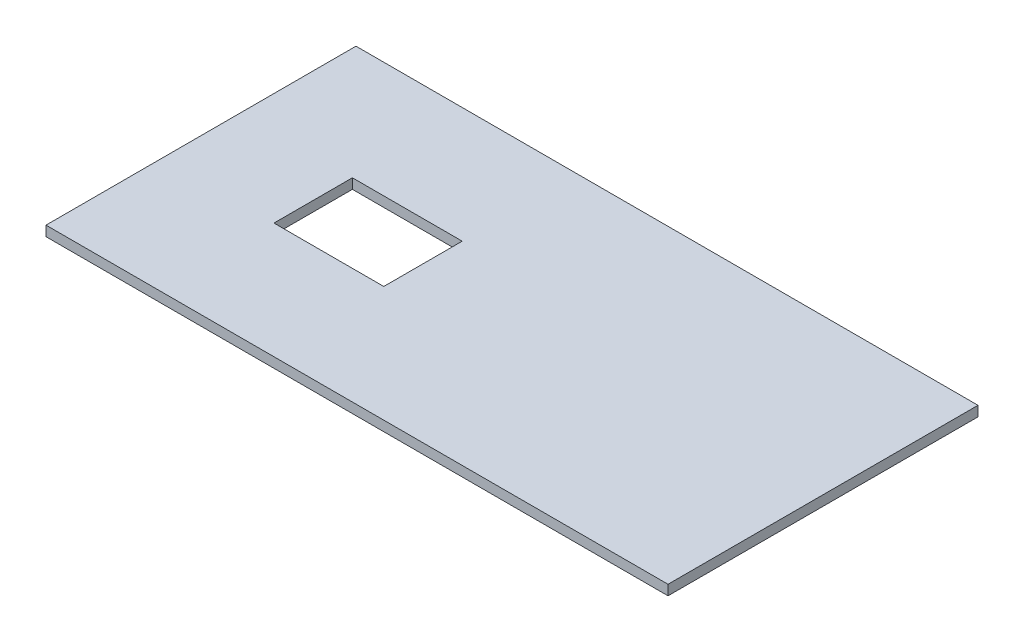
SolidWorks part; units mm, degrees
ref_plane "Front Plane" through (0, 0, 0) normal (0, 0, 1) x (1, 0, 0)
ref_plane "Top Plane" through (0, 0, 0) normal (0, 1, 0) x (1, 0, 0)
ref_plane "Right Plane" through (0, 0, 0) normal (1, 0, 0) x (0, 0, -1)
sketch "Sketch1" plane through (0, 0, 0) normal (0, 1, 0) x (1, 0, 0)
  line L1 (-56.3382, 28.5039) -> (141.9218, 28.5039)
  line L2 (-56.3382, 28.5039) -> (-56.3382, -70.2961)
  line L3 (-56.3382, -70.2961) -> (141.9218, -70.2961)
  line L4 (141.9218, 28.5039) -> (141.9218, -70.2961)
  line L5 (-20.5782, -8.3961) -> (14.4218, -8.3961)
  line L6 (-20.5782, -8.3961) -> (-20.5782, -33.3961)
  line L7 (-20.5782, -33.3961) -> (14.4218, -33.3961)
  line L8 (14.4218, -8.3961) -> (14.4218, -33.3961)
  point P8 (-3.0782, -33.3961)
  point P9 (-56.3382, -20.8961)
  point P10 (-20.5782, -20.8961)
  dimension "D1" = 198.26
  dimension "D2" = 98.8
  dimension "D3" = 35
  dimension "D4" = 25
  dimension "D5" = 145
extrude "Boss-Extrude1" add sketch "Sketch1" along normal blind 3.2
equation "\"Fit\"= 1"
equation "\"cover width\"= 98.8"
equation "\"bottom 7 length\"= 198.26"
equation "\"thinner acrylic\"= 3.2"
equation "\"D1@Sketch1\"=\"bottom 7 length\""
equation "\"D2@Sketch1\"=\"cover width\""
equation "\"D1@Boss-Extrude1\"=\"thinner acrylic\""
equation "\"camera hole width\" = 25"
equation "\"camera hole length\"= 35"
equation "\"camera hole from bottom\"= 145"
equation "\"D3@Sketch1\"=\"camera hole length\""
equation "\"D4@Sketch1\"=\"camera hole width\""
equation "\"D5@Sketch1\"=\"camera hole from bottom\""
